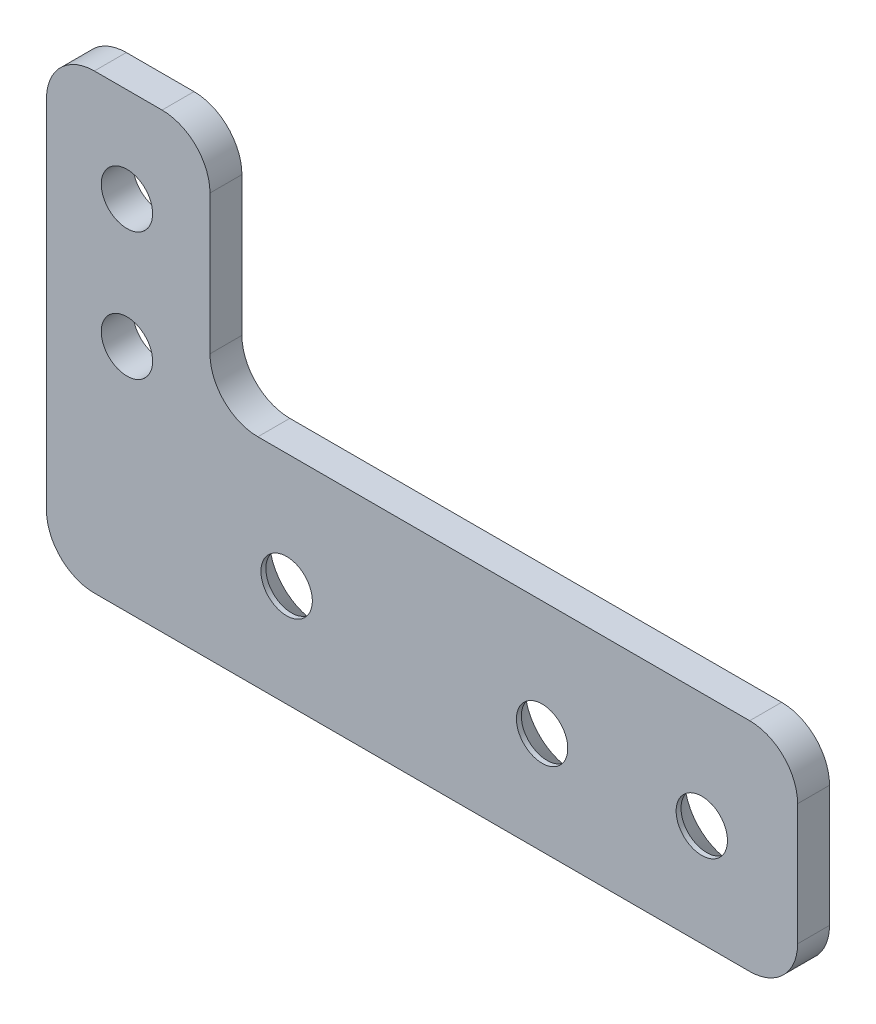
SolidWorks part; units mm, degrees
material "6061-T6 (SS)"
ref_plane "Front Plane" through (0, 0, 0) normal (0, 0, 1) x (1, 0, 0)
ref_plane "Top Plane" through (0, 0, 0) normal (0, 1, 0) x (1, 0, 0)
ref_plane "Right Plane" through (0, 0, 0) normal (1, 0, 0) x (0, 0, -1)
sketch "Sketch1" plane through (0, 0, 0) normal (0, 0, 1) x (1, 0, 0)
  line L0 (41.275, -11.049) -> (-33.401, -11.049) construction
  line L1 (-41.275, -23.749) -> (41.275, -23.749)
  line L2 (-41.275, -23.749) -> (-41.275, 23.749)
  line L3 (-41.275, 23.749) -> (41.275, 23.749)
  line L4 (41.275, -23.749) -> (41.275, 23.749)
  line L5 (-41.275, -23.749) -> (41.275, 23.749) construction
  line L6 (-41.275, 23.749) -> (41.275, -23.749) construction
  line L7 (41.275, 23.749) -> (-17.145, 23.749)
  line L8 (41.275, 23.749) -> (41.275, 0.381)
  line L9 (41.275, 0.381) -> (-17.145, 0.381)
  line L10 (-17.145, 23.749) -> (-17.145, 0.381)
  line L11 (-41.275, -23.749) -> (-33.401, -23.749)
  line L12 (-41.275, -23.749) -> (-41.275, 23.749)
  line L13 (-41.275, 23.749) -> (-33.401, 23.749)
  line L14 (-33.401, -23.749) -> (-33.401, 23.749)
  line L15 (-33.401, -23.749) -> (41.275, -23.749)
  line L16 (-33.401, -23.749) -> (-33.401, -21.209)
  line L17 (-33.401, -21.209) -> (41.275, -21.209)
  line L18 (41.275, -23.749) -> (41.275, -21.209)
  line L19 (-33.401, 23.876) -> (-17.145, 23.876) construction
  circle A0 centre (-25.4, -11.049) radius 2.5527
  circle A1 centre (-25.4, 1.651) radius 2.5527
  circle A2 centre (-25.4, 14.351) radius 2.5527
  point P0 (0, 0)
  point P22 (31.75, -11.049)
  point P23 (-9.525, -11.049)
  point P24 (15.875, -11.049)
  dimension "D7" = 5.1054
  dimension "D1" = 82.55
  dimension "D2" = 47.498
  dimension "D3" = 24.13
  dimension "D4" = 24.13
  dimension "D5" = 7.874
  dimension "D6" = 47.498
  dimension "D8" = 15.875
  dimension "D9" = 12.7
  dimension "D10" = 12.7
  dimension "D11" = 12.7
  dimension "D12" = 9.525
  dimension "D13" = 41.275
  dimension "D14" = 25.4
  dimension "D15" = 8.001
  dimension "D16" = 2.54
extrude "Boss-Extrude1" add sketch "Sketch1" along normal blind 3.175 contours L14 L17 L4 L9 L10 L3 A2 A1 A0 | A0 region at (-0.8769, -6.375, 0) region at (-25.4, -11.049, 0)
fillet "Fillet1" radius 4.7625 6 edges at (-33.401, 23.749, 1.5875) (-17.145, 23.749, 1.5875) (-17.145, 0.381, 1.5875) (41.275, 0.381, 1.5875) (41.275, -21.209, 1.5875) (-33.401, -21.209, 1.5875)
hole_wizard "CSK for #10 Flat Head Machine Screw3" positions "Sketch6" profile "Sketch7" countersink size "#10" standard "ANSI Inch" end condition through all
sketch "Sketch6" plane through (0, 0, 0) normal (0, 0, -1) x (-1, 0, 0)
  point P0 (-31.75, -11.049)
  point P3 (-15.875, -11.049)
  point P6 (9.525, -11.049)
sketch "Sketch7" plane through (31.75, -11.049, 0) normal (1, 0, 0) x (0, 1, 0)
  line L0 (0, 0) -> (0, 3.175)
  line L1 (0, 3.175) -> (2.5527, 3.175)
  line L2 (2.5527, 3.175) -> (2.5527, 2.6882)
  line L3 (2.5527, 2.6882) -> (4.8895, 0)
  line L5 (4.8895, 0) -> (0, 0)
  line L6 (-2.5527, 2.6882) -> (-4.8895, 0) construction
  line L11 (0, -6.35) -> (0, 107.95) construction
  dimension "Thru Hole Dia." = 5.1054
  dimension "Thru Hole Depth" = 3.175
  dimension "Near C'Sink Dia." = 9.779
  dimension "Near C'Sink Angle" = 82
